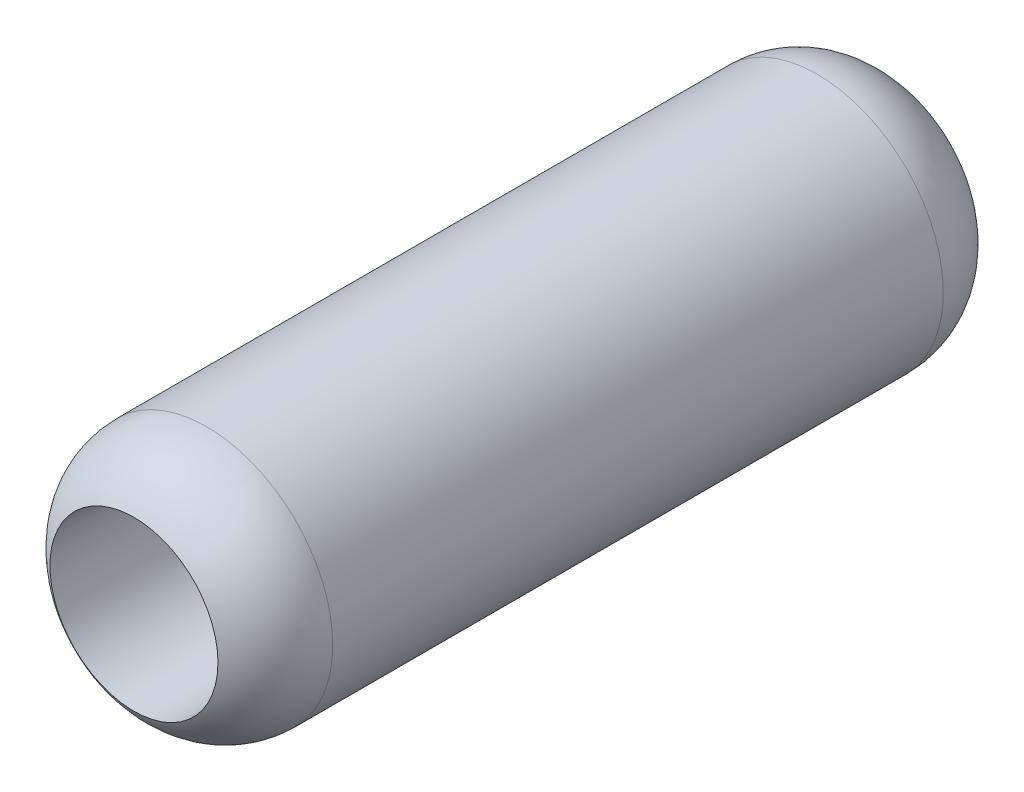
SolidWorks part; units mm, degrees
ref_plane "Front Plane" through (0, 0, 0) normal (0, 0, 1) x (1, 0, 0)
ref_plane "Top Plane" through (0, 0, 0) normal (0, 1, 0) x (1, 0, 0)
ref_plane "Right Plane" through (0, 0, 0) normal (1, 0, 0) x (0, 0, -1)
sketch "Sketch1" plane through (0, 0, 0) normal (0, 0, 1) x (1, 0, 0)
  circle A0 centre (-0.0032, -0.0036) radius 1.5
  circle A1 centre (-0.0032, -0.0036) radius 1
  dimension "D1" = 3
  dimension "D2" = 2
  dimension "D3" = 0
extrude "Boss-Extrude1" add sketch "Sketch1" along normal blind 9
fillet "Fillet1" radius 1 2 edges at (1.4968, -0.0036, 0) (1.4968, -0.0036, 9)
